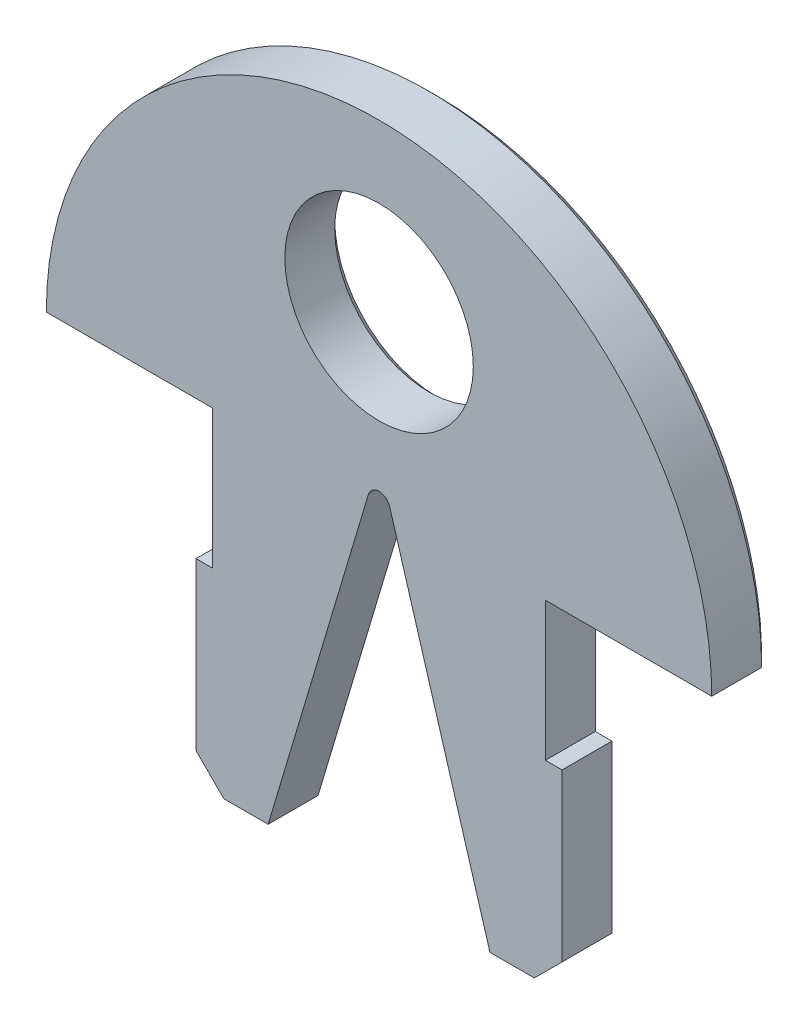
SolidWorks part; units mm, degrees
material "Custom Plastic"
ref_plane "Front Plane" through (0, 0, 0) normal (0, 0, 1) x (1, 0, 0)
ref_plane "Top Plane" through (0, 0, 0) normal (0, 1, 0) x (1, 0, 0)
ref_plane "Right Plane" through (0, 0, 0) normal (1, 0, 0) x (0, 0, -1)
sketch "Sketch1" plane through (0, 0, 0) normal (0, 0, 1) x (1, 0, 0)
  line L0 (6, 6) -> (12, 6)
  line L1 (-6, -6) -> (-6.6, -6)
  line L2 (-6, 6) -> (-6, 1)
  line L3 (-6, -6) -> (-4, -6)
  line L4 (6, 6) -> (6, 1)
  line L5 (-6, 6) -> (6, -6) construction
  line L6 (-6, -6) -> (6, 6) construction
  line L7 (-12, 18) -> (12, 18) construction
  line L8 (-4, -6) -> (-0.3833, 6.1144)
  line L9 (-12, 6) -> (-6, 6)
  line L10 (0.3833, 6.1144) -> (4, -6)
  line L11 (-12, 18) -> (12, 6) construction
  line L12 (-12, 6) -> (12, 18) construction
  line L14 (-6, 1) -> (-6.6, 1)
  line L15 (-6.6, -6) -> (-6.6, 1)
  line L16 (6, -6) -> (6.6, -6)
  line L18 (6, 1) -> (6.6, 1)
  line L19 (6.6, -6) -> (6.6, 1)
  line L20 (4, -6) -> (6, -6)
  arc A0 (0.3833, 6.1144) -> (-0.3833, 6.1144) centre (0, 6) ccw
  circle A1 centre (0, 12) radius 3.3993
  arc A2 (12, 6) -> (-12, 6) centre (0, 6) ccw
  point P0 (0, 0)
  point P6 (0, 12)
  dimension "D7" = 0.8
  dimension "D1" = 12
  dimension "D2" = 12
  dimension "D3" = 24
  dimension "D4" = 12
  dimension "D5" = 0.6
  dimension "D6" = 5
  dimension "D8" = 2
extrude "Boss-Extrude1" add sketch "Sketch1" along normal blind 2.1
chamfer "Chamfer1" distance 1 angle 45 2 edges at (6.6, -6, 1.05) (-6.6, -6, 1.05)
chamfer "Chamfer2" distance 0.3 angle 45 17 edges at (3.3993, 12, 0) (6.3, 1, 0) (6, 3.5, 0) (9, 6, 0) (0, 18, 0) (-9, 6, 0) (-6, 3.5, 0) (-6.3, 1, 0) (-6.6, -2, 0) (-6.1, -5.5, 0) (-4.8, -6, 0) (-2.1916, 0.0572, 0) (0, 6.4, 0) (2.1916, 0.0572, 0) (4.8, -6, 0) (6.1, -5.5, 0) (6.6, -2, 0)
